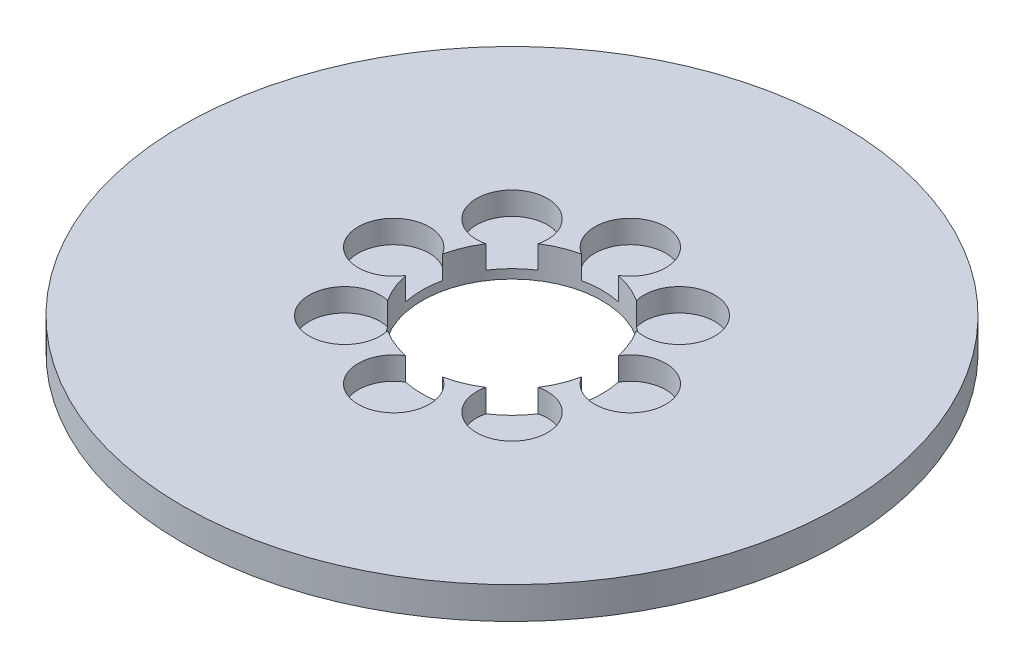
SolidWorks part; units mm, degrees
ref_plane "Front Plane" through (0, 0, 0) normal (0, 0, 1) x (1, 0, 0)
ref_plane "Top Plane" through (0, 0, 0) normal (0, 1, 0) x (1, 0, 0)
ref_plane "Right Plane" through (0, 0, 0) normal (1, 0, 0) x (0, 0, -1)
sketch "Sketch1" plane through (0, 0, 0) normal (0, 1, 0) x (1, 0, 0)
  circle A0 centre (0, 0) radius 82.5
  dimension "FLANGE_OD" = 165
extrude "Boss-Extrude1" add sketch "Sketch1" along normal blind 8
sketch "Sketch2" plane through (0, 0, 0) normal (0, 1, 0) x (1, 0, 0)
  circle A0 centre (0, 0) radius 22.5
  dimension "BORE_D" = 45
extrude "Cut-Extrude1" cut sketch "Sketch2" along normal through all
sketch "Sketch3" plane through (0, 8, 0) normal (0, 1, 0) x (1, 0, 0)
  circle A0 centre (0, 0) radius 29.6132 construction
  circle A1 centre (-29.6132, 0) radius 8.8919
  dimension "BOLT_D" = 17.7838
  dimension "BOLT_PCD" = 59.2264
extrude "Cut-Extrude2" cut sketch "Sketch3" against normal blind 5.7316
pattern_circular "CirPattern1" count 8 over 360 about axis through (0, 0, 0) along (0, 1, 0) of "Cut-Extrude2"
